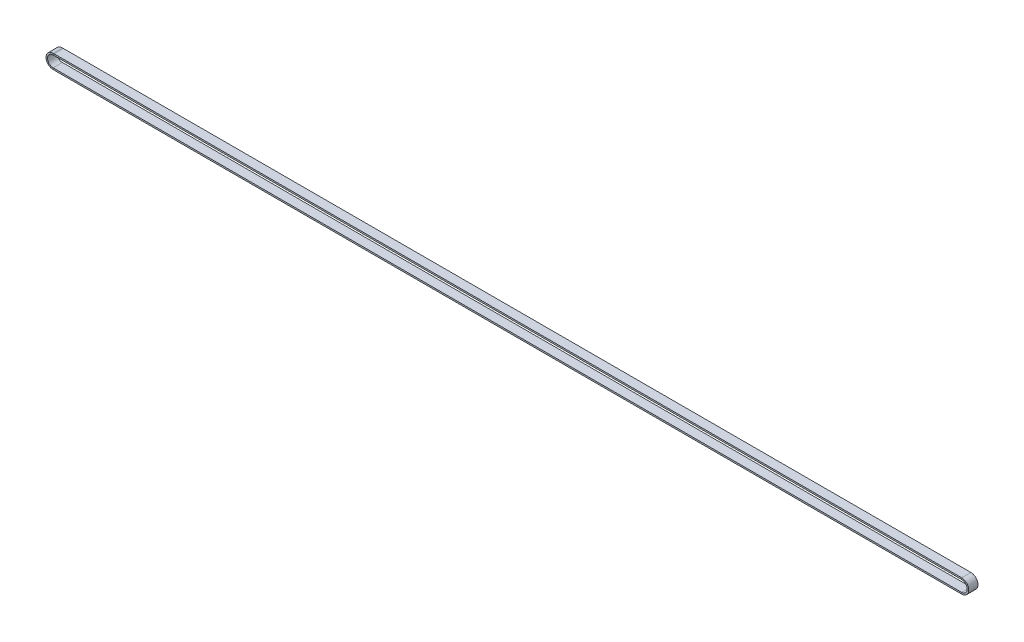
SolidWorks part; units mm, degrees
ref_plane "Front Plane" through (0, 0, 0) normal (0, 0, 1) x (1, 0, 0)
ref_plane "Top Plane" through (0, 0, 0) normal (0, 1, 0) x (1, 0, 0)
ref_plane "Right Plane" through (0, 0, 0) normal (1, 0, 0) x (0, 0, -1)
sketch "Sketch2" plane through (0, 0, 0) normal (0, 0, 1) x (1, 0, 0)
  line L0 (0, 0) -> (1, 0) construction
  line L1 (0, 0) -> (0, 1) construction
  line L2 (-1, -26.89) -> (883.5206, -26.89)
  line L3 (883.5206, -40.69) -> (-1, -40.69)
  arc A0 (-1, -40.69) -> (-1, -26.89) centre (-1, -33.79) cw
  arc A1 (883.5206, -26.89) -> (883.5206, -40.69) centre (883.5206, -33.79) cw
sketch "Sketch3" plane through (0, 0, 0) normal (1, 0, 0) x (0, 0, -1)
  line L1 (0, -28.39) -> (-9, -28.39)
  line L2 (0, -28.39) -> (0, -26.89)
  line L3 (0, -26.89) -> (-9, -26.89)
  line L4 (-9, -28.39) -> (-9, -26.89)
  dimension "D1" = 9
  dimension "D2" = 1.5
sweep "Sweep1" add profiles "Sketch3" path "Sketch2"
